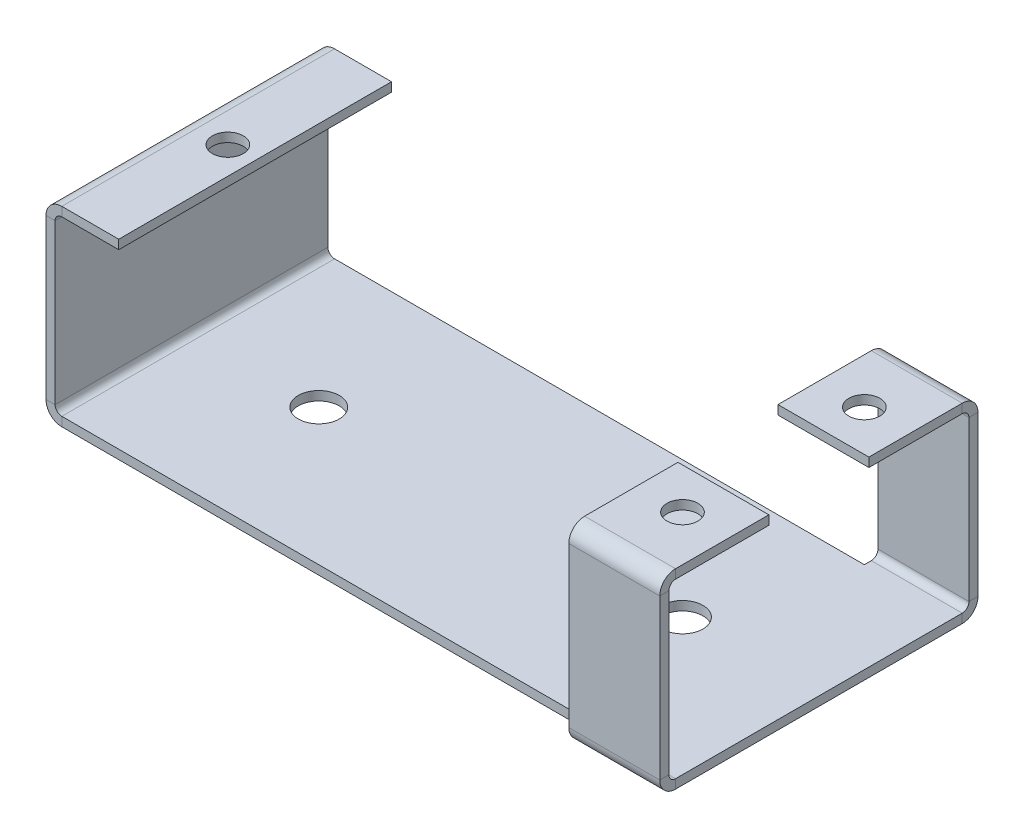
SolidWorks part; units mm, degrees
note: The reader was unsure of these and kept them because the rebuilt part matched: flange length of "Tôle pliée sur arête1", "Tôle pliée sur arête2", "Tôle pliée sur arête3", "Tôle pliée sur arête4".
ref_plane "Plan de face" through (0, 0, 0) normal (0, 0, 1) x (1, 0, 0)
ref_plane "Plan de dessus" through (0, 0, 0) normal (0, 1, 0) x (1, 0, 0)
ref_plane "Plan de droite" through (0, 0, 0) normal (1, 0, 0) x (0, 0, -1)
sketch "Esquisse1" plane through (0, 0, 0) normal (0, 1, 0) x (1, 0, 0)
  line L0 (35, -15) -> (35, -16.5)
  line L1 (-35, -15) -> (25, -15)
  line L2 (-35, -15) -> (-35, 15)
  line L3 (-35, 15) -> (25, 15)
  line L4 (35, -15) -> (35, 15)
  line L5 (-35, -15) -> (35, 15) construction
  line L6 (-35, 15) -> (35, -15) construction
  line L7 (35, -16.5) -> (25, -16.5)
  line L8 (25, -16.5) -> (25, -15)
  line L9 (-11.55, 0) -> (11.55, 0) construction
  line L10 (35, 15) -> (35, 16.5)
  line L11 (35, 16.5) -> (25, 16.5)
  line L12 (25, 16.5) -> (25, 15)
  point P0 (0, 0)
  dimension "D1" = 30
  dimension "D2" = 70
  dimension "D3" = 1.5
  dimension "D4" = 10
base flange "Tôle de base pliée1" sketch "Esquisse1" thickness 1 reverse thickness direction yes parameters "D1"=0.7366
edge flange "Tôle pliée sur arête1" sketch "Esquisse8" flange angle 90 flange length 20 flange position material inside bend radius 0.7366 thickness 1 relief rectangular parameters "D6"=10
sketch "Esquisse8" plane through (-35, 1, 0) normal (-1, 0, 0) x (0, 0, 1)
  line L0 (-15, 0) -> (15, 0) construction
  line L1 (-15, 0) -> (15, 0)
  line L2 (-15, 0) -> (-15, 20)
  line L3 (-15, 20) -> (15, 20)
  line L4 (15, 20) -> (15, 0)
bend "Pli d'arête1" bend radius 0.7366 bend angle 90 parameters "D5"=1
edge flange "Tôle pliée sur arête2" sketch "Esquisse11" flange angle 90 flange length 8 flange position material inside bend radius 0.7366 thickness 1 relief rectangular parameters "D6"=10
sketch "Esquisse11" plane through (-34, 21, 0) normal (0, 1, 0) x (0, 0, 1)
  line L0 (15, 0) -> (-15, 0) construction
  line L1 (15, 0) -> (-15, 0)
  line L2 (-15, 0) -> (-15, 7)
  line L3 (-15, 7) -> (15, 7)
  line L4 (15, 7) -> (15, 0)
bend "Pli d'arête2" bend radius 0.7366 bend angle 90 parameters "D5"=2
sketch "Esquisse12" plane through (0, 21, 0) normal (0, 1, 0) x (1, 0, 0)
  line L0 (-11.55, 0) -> (11.55, 0) construction
  line L7 (-35, -15) -> (-35, 15) construction
  circle A2 centre (-30, 0) radius 1.7
  dimension "D2" = 5
  dimension "D1" = 3.4
extrude "Enlèv. mat.-Extru.1" cut sketch "Esquisse12" against normal up to next normal cut yes
sketch "Esquisse27" plane through (0, 1, 0) normal (0, 1, 0) x (1, 0, 0)
  line L0 (-11.55, 0) -> (11.55, 0) construction
  line L1 (0, -11.55) -> (0, 11.55) construction
  circle A0 centre (-20, 0) radius 2.25
  circle A1 centre (20, 0) radius 2.25
  dimension "D1" = 4.5
  dimension "D2" = 20
extrude "Enlèv. mat.-Extru.3" cut sketch "Esquisse27" against normal up to next normal cut yes
edge flange "Tôle pliée sur arête3" sketch "Esquisse18" flange profiles "Esquisse18", "Esquisse19" flange angle 90 flange length 19 flange position material outside bend radius 0.7366 thickness 1 relief rectangular parameters "D6"=10, "D8"=1
sketch "Esquisse18" plane through (0, 1, 16.5) normal (0, 0, 1) x (1, 0, 0)
  line L0 (25, 0) -> (35, 0) construction
  line L1 (25, 0) -> (35, 0)
  line L2 (25, 0) -> (25, 19)
  line L3 (25, 19) -> (35, 19)
  line L4 (35, 19) -> (35, 0)
sketch "Esquisse19" plane through (0, 1, -16.5) normal (0, 0, -1) x (-1, 0, 0)
  line L0 (-35, 0) -> (-25, 0) construction
  line L1 (-35, 0) -> (-25, 0)
  line L2 (-35, 0) -> (-35, 19)
  line L3 (-35, 19) -> (-25, 19)
  line L4 (-25, 19) -> (-25, 0)
bend "Pli d'arête3" bend radius 0.7366 bend angle 90 parameters "D5"=3
bend "Pli d'arête4" bend radius 0.7366 bend angle 90 parameters "D5"=4
edge flange "Tôle pliée sur arête4" sketch "Esquisse24" flange profiles "Esquisse24", "Esquisse25" flange angle 90 flange length 11 flange position material outside bend radius 0.7366 thickness 1 relief rectangular parameters "D6"=10, "D8"=1
sketch "Esquisse24" plane through (0, 20, 16.5) normal (0, 1, 0) x (1, 0, 0)
  line L0 (35, 0) -> (25, 0) construction
  line L1 (35, 0) -> (25, 0)
  line L2 (25, 0) -> (25, 11)
  line L3 (25, 11) -> (35, 11)
  line L4 (35, 11) -> (35, 0)
sketch "Esquisse25" plane through (0, 20, -16.5) normal (0, 1, 0) x (-1, 0, 0)
  line L0 (-25, 0) -> (-35, 0) construction
  line L1 (-25, 0) -> (-35, 0)
  line L2 (-35, 0) -> (-35, 11)
  line L3 (-35, 11) -> (-25, 11)
  line L4 (-25, 11) -> (-25, 0)
bend "Pli d'arête5" bend radius 0.7366 bend angle 90 parameters "D5"=5
bend "Pli d'arête6" bend radius 0.7366 bend angle 90 parameters "D5"=6
sketch "Esquisse26" plane through (0, 21, 0) normal (0, 1, 0) x (1, 0, 0)
  line L0 (30, -5.5) -> (30, -15) construction
  line L1 (25, -5.5) -> (35, -5.5) construction
  line L3 (-33.2634, -15) -> (25, -15) construction
  line L4 (-11.55, 0) -> (11.55, 0) construction
  circle A0 centre (30, -10) radius 1.7
  circle A1 centre (30, 10) radius 1.7
  dimension "D1" = 3.4
  dimension "D2" = 5
extrude "Enlèv. mat.-Extru.2" cut sketch "Esquisse26" against normal up to next normal cut yes
sketch "Lignes de pliage1" [suppressed] plane through (0, 0, 0) normal (0, 1, 0) x (1, 0, 0)
sketch "Cube de visualisation1" [suppressed] plane through (0, 0, 0) normal (0, 1, 0) x (1, 0, 0)
sheet metal parameters "Tôlerie1" thickness 1 parameters "D1"=0.7366
flat pattern "Etat déplié1" [suppressed]
sketch "Lignes de pliage2" plane through (0, 0, 0) normal (0, 1, 0) x (1, 0, 0)
sketch3d "Cube de visualisation2" [suppressed]
  line L0 (26.75, 15, 0) -> (-26.75, 15, 0) construction
  line L1 (26.75, -15, 0) -> (-26.75, -15, 0) construction
  line L2 (26.75, 15, 0) -> (26.75, -15, 0) construction
  line L3 (-26.75, 15, 0) -> (-26.75, -15, 0) construction
sheet metal parameters "Tôlerie2" thickness 1 parameters "D1"=0.7366
flat pattern "Etat déplié1"
sketch "Lignes de pliage2" plane through (0, 0, 0) normal (0, -1, 0) x (-1, 0, 0)
  line L0 (26.9846, -15) -> (26.9846, 15) construction
  line L1 (26.9846, -15) -> (26.9846, 15) construction
sketch3d "Cube de visualisation2" [suppressed]
  line L0 (-26.75, 15, 0) -> (46.2192, 15, 0) construction
  line L1 (-26.75, -15, 0) -> (46.2192, -15, 0) construction
  line L2 (-26.75, 15, 0) -> (-26.75, -15, 0) construction
  line L3 (46.2192, 15, 0) -> (46.2192, -15, 0) construction
bend of the flat pattern "Dépliage-<Pli d'arête1>1"
sheet metal parameters "Tôlerie3" thickness 1 parameters "D1"=0.7366
flat pattern "Etat déplié1"
sketch "Lignes de pliage2" plane through (0, 0, 0) normal (0, -1, 0) x (-1, 0, 0)
  line L0 (26.9846, -15) -> (26.9846, 15) construction
  line L1 (26.9846, -15) -> (26.9846, 15) construction
  line L2 (45.4539, -15) -> (45.4539, 15) construction
  line L3 (45.4539, -15) -> (45.4539, 15) construction
sketch3d "Cube de visualisation2" [suppressed]
  line L0 (-26.75, 15, 0) -> (51.6885, 15, 0) construction
  line L1 (-26.75, -15, 0) -> (51.6885, -15, 0) construction
  line L2 (-26.75, 15, 0) -> (-26.75, -15, 0) construction
  line L3 (51.6885, 15, 0) -> (51.6885, -15, 0) construction
bend of the flat pattern "Dépliage-<Pli d'arête1>1"
bend of the flat pattern "Dépliage-<Pli d'arête2>1"
sheet metal parameters "Tôlerie4" thickness 1 parameters "D1"=0.7366
flat pattern "Etat déplié1"
sketch "Lignes de pliage2" plane through (0, 0, 0) normal (0, -1, 0) x (-1, 0, 0)
  line L0 (26.9846, -15) -> (26.9846, 15) construction
  line L1 (26.9846, -15) -> (26.9846, 15) construction
  line L2 (45.4539, -15) -> (45.4539, 15) construction
  line L3 (45.4539, -15) -> (45.4539, 15) construction
sketch3d "Cube de visualisation2" [suppressed]
  line L0 (-26.75, -16.5, 0) -> (51.6885, -16.5, 0) construction
  line L1 (-26.75, 16.5, 0) -> (51.6885, 16.5, 0) construction
  line L2 (-26.75, -16.5, 0) -> (-26.75, 16.5, 0) construction
  line L3 (51.6885, -16.5, 0) -> (51.6885, 16.5, 0) construction
bend of the flat pattern "Dépliage-<Pli d'arête1>1"
bend of the flat pattern "Dépliage-<Pli d'arête2>1"
sheet metal parameters "Tôlerie5" thickness 1 parameters "D1"=0.7366
flat pattern "Etat déplié1"
sketch "Lignes de pliage2" plane through (0, 0, 0) normal (0, -1, 0) x (-1, 0, 0)
  line L0 (26.9846, -15) -> (26.9846, 15) construction
  line L1 (26.9846, -15) -> (26.9846, 15) construction
  line L2 (45.4539, -15) -> (45.4539, 15) construction
  line L3 (45.4539, -15) -> (45.4539, 15) construction
  line L4 (-20.75, 16.7346) -> (-26.75, 16.7346) construction
  line L5 (-26.75, -16.7346) -> (-20.75, -16.7346) construction
  line L6 (-20.75, 16.7346) -> (-26.75, 16.7346) construction
  line L7 (-26.75, -16.7346) -> (-20.75, -16.7346) construction
sketch3d "Cube de visualisation2" [suppressed]
  line L0 (-26.75, -35.9692, 0) -> (51.6885, -35.9692, 0) construction
  line L1 (-26.75, 35.9692, 0) -> (51.6885, 35.9692, 0) construction
  line L2 (-26.75, -35.9692, 0) -> (-26.75, 35.9692, 0) construction
  line L3 (51.6885, -35.9692, 0) -> (51.6885, 35.9692, 0) construction
bend of the flat pattern "Dépliage-<Pli d'arête1>1"
bend of the flat pattern "Dépliage-<Pli d'arête2>1"
bend of the flat pattern "Dépliage-<Pli d'arête3>1"
bend of the flat pattern "Dépliage-<Pli d'arête4>1"
sheet metal parameters "Tôlerie6" thickness 1 parameters "D1"=0.7366
flat pattern "Etat déplié1"
sketch "Lignes de pliage2" plane through (0, 0, 0) normal (0, -1, 0) x (-1, 0, 0)
  line L0 (26.9846, -15) -> (26.9846, 15) construction
  line L1 (26.9846, -15) -> (26.9846, 15) construction
  line L2 (46.4539, -15) -> (46.4539, 15) construction
  line L3 (46.4539, -15) -> (46.4539, 15) construction
  line L4 (-20.75, 16.7346) -> (-26.75, 16.7346) construction
  line L5 (-26.75, -16.7346) -> (-20.75, -16.7346) construction
  line L6 (-20.75, 16.7346) -> (-26.75, 16.7346) construction
  line L7 (-26.75, -16.7346) -> (-20.75, -16.7346) construction
  line L8 (-20.75, 35.2039) -> (-26.75, 35.2039) construction
  line L9 (-26.75, -35.2039) -> (-20.75, -35.2039) construction
  line L10 (-20.75, 35.2039) -> (-26.75, 35.2039) construction
  line L11 (-26.75, -35.2039) -> (-20.75, -35.2039) construction
sketch3d "Cube de visualisation2" [suppressed]
  line L0 (52.6885, 43.4385, 0) -> (52.6885, -43.4385, 0) construction
  line L1 (-26.75, 43.4385, 0) -> (-26.75, -43.4385, 0) construction
  line L2 (52.6885, 43.4385, 0) -> (-26.75, 43.4385, 0) construction
  line L3 (52.6885, -43.4385, 0) -> (-26.75, -43.4385, 0) construction
bend of the flat pattern "Dépliage-<Pli d'arête1>1"
bend of the flat pattern "Dépliage-<Pli d'arête2>1"
bend of the flat pattern "Dépliage-<Pli d'arête3>1"
bend of the flat pattern "Dépliage-<Pli d'arête4>1"
bend of the flat pattern "Dépliage-<Pli d'arête5>1"
bend of the flat pattern "Dépliage-<Pli d'arête6>1"
sheet metal parameters "Tôlerie7" thickness 1 parameters "D1"=0.7366
flat pattern "Etat déplié1"
sketch "Lignes de pliage2" plane through (0, 0, 0) normal (0, -1, 0) x (-1, 0, 0)
  line L0 (34.2346, -15) -> (34.2346, 15) construction
  line L1 (34.2346, -15) -> (34.2346, 15) construction
  line L2 (53.7039, -15) -> (53.7039, 15) construction
  line L3 (53.7039, -15) -> (53.7039, 15) construction
  line L4 (-25, 16.7346) -> (-35, 16.7346) construction
  line L5 (-35, -16.7346) -> (-25, -16.7346) construction
  line L6 (-25, 16.7346) -> (-35, 16.7346) construction
  line L7 (-35, -16.7346) -> (-25, -16.7346) construction
  line L8 (-25, 36.2039) -> (-35, 36.2039) construction
  line L9 (-35, -36.2039) -> (-25, -36.2039) construction
  line L10 (-25, 36.2039) -> (-35, 36.2039) construction
  line L11 (-35, -36.2039) -> (-25, -36.2039) construction
sketch3d "Cube de visualisation2" [suppressed]
  line L0 (-35, -47.4385, 0) -> (60.9385, -47.4385, 0) construction
  line L1 (-35, 47.4385, 0) -> (60.9385, 47.4385, 0) construction
  line L2 (-35, -47.4385, 0) -> (-35, 47.4385, 0) construction
  line L3 (60.9385, -47.4385, 0) -> (60.9385, 47.4385, 0) construction
bend of the flat pattern "Dépliage-<Pli d'arête1>1"
bend of the flat pattern "Dépliage-<Pli d'arête2>1"
bend of the flat pattern "Dépliage-<Pli d'arête3>1"
bend of the flat pattern "Dépliage-<Pli d'arête4>1"
bend of the flat pattern "Dépliage-<Pli d'arête5>1"
bend of the flat pattern "Dépliage-<Pli d'arête6>1"
sheet metal parameters "Tôlerie8" thickness 1 parameters "D1"=0.7366
flat pattern "Etat déplié1"
sketch "Lignes de pliage2" plane through (0, 0, 0) normal (0, -1, 0) x (-1, 0, 0)
  line L0 (26.9846, -15) -> (26.9846, 15) construction
  line L1 (26.9846, -15) -> (26.9846, 15) construction
  line L2 (46.4539, -15) -> (46.4539, 15) construction
  line L3 (46.4539, -15) -> (46.4539, 15) construction
  line L4 (-20.75, 16.7346) -> (-26.75, 16.7346) construction
  line L5 (-26.75, -16.7346) -> (-20.75, -16.7346) construction
  line L6 (-20.75, 16.7346) -> (-26.75, 16.7346) construction
  line L7 (-26.75, -16.7346) -> (-20.75, -16.7346) construction
  line L8 (-20.75, 35.2039) -> (-26.75, 35.2039) construction
  line L9 (-26.75, -35.2039) -> (-20.75, -35.2039) construction
  line L10 (-20.75, 35.2039) -> (-26.75, 35.2039) construction
  line L11 (-26.75, -35.2039) -> (-20.75, -35.2039) construction
sketch3d "Cube de visualisation2" [suppressed]
  line L0 (52.6885, 43.4385, 0) -> (52.6885, -43.4385, 0) construction
  line L1 (-26.75, 43.4385, 0) -> (-26.75, -43.4385, 0) construction
  line L2 (52.6885, 43.4385, 0) -> (-26.75, 43.4385, 0) construction
  line L3 (52.6885, -43.4385, 0) -> (-26.75, -43.4385, 0) construction
bend of the flat pattern "Dépliage-<Pli d'arête1>1"
bend of the flat pattern "Dépliage-<Pli d'arête2>1"
